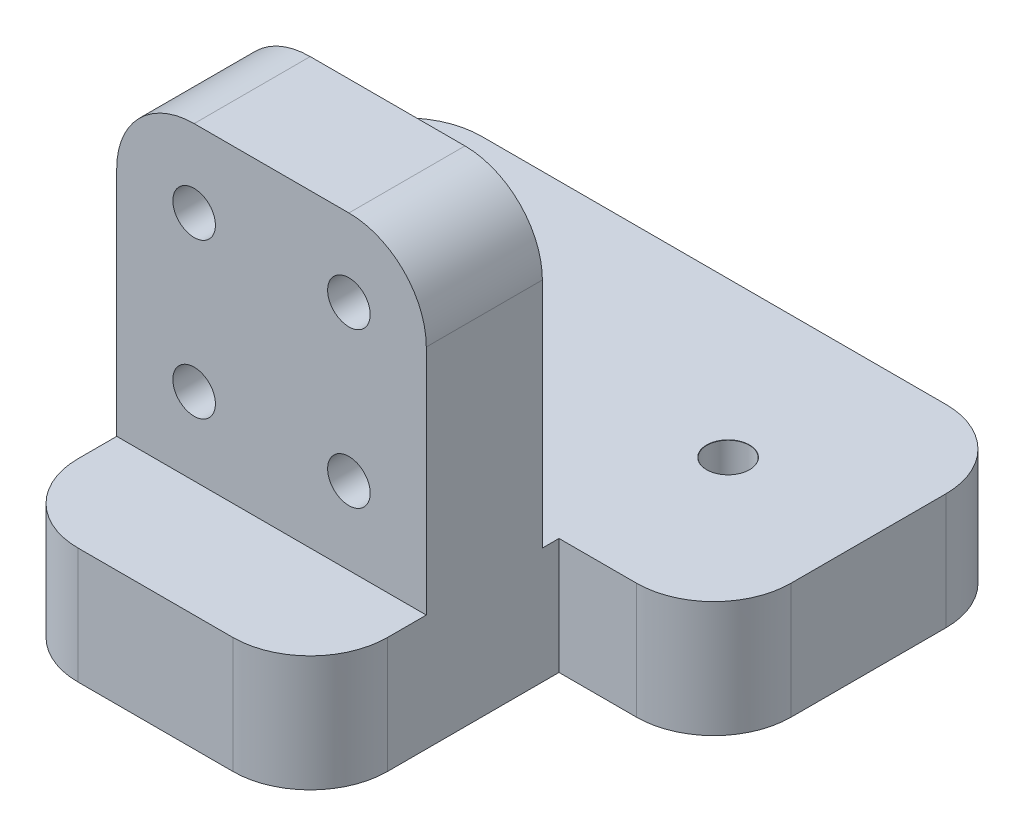
SolidWorks part; units mm, degrees
ref_plane "Front Plane" through (0, 0, 0) normal (0, 0, 1) x (1, 0, 0)
ref_plane "Top Plane" through (0, 0, 0) normal (0, 1, 0) x (1, 0, 0)
ref_plane "Right Plane" through (0, 0, 0) normal (1, 0, 0) x (0, 0, -1)
sketch "Sketch1" plane through (0, 0, 0) normal (0, 1, 0) x (1, 0, 0)
  line L1 (0, 0) -> (40, 0)
  line L7 (40, 0) -> (40, 32.15)
  line L8 (0, 0) -> (0, 32.15)
  line L13 (0, 32.15) -> (-20, 32.15)
  line L14 (-20, 32.15) -> (-20, 72.15)
  line L15 (-20, 72.15) -> (60, 72.15)
  line L16 (60, 72.15) -> (60, 32.15)
  line L17 (60, 32.15) -> (40, 32.15)
  line L18 (-1.85, 52.15) -> (41.85, 52.15) construction
  point P1 (41.85, 52.15)
  point P12 (-1.85, 52.15)
  point P13 (-20, 52.15)
  point P16 (20, 72.15)
  point P17 (20, 52.15)
  dimension "D1" = 40
  dimension "D2" = 52.15
  dimension "D3" = 40
  dimension "D4" = 43.7
  dimension "D5" = 20
extrude "Boss-Extrude1" add sketch "Sketch1" along normal blind 15 contours L1 region at (20, 0, -41.8084)
sketch "Sketch6" plane through (0, 15, 0) normal (0, 1, 0) x (1, 0, 0)
  point P0 (-1.85, 52.15)
  point P3 (41.85, 52.15)
hole_wizard "M5 Clearance Hole1" positions "Sketch6" profile "Sketch5" hole size "M5" standard "ANSI Metric" end condition through all
sketch "Sketch5" plane through (-1.85, 15, -52.15) normal (1, 0, 0) x (0, 0, 1)
  line L0 (0, 0) -> (0, 15)
  line L1 (0, 15) -> (2.75, 15)
  line L2 (2.75, 15) -> (2.75, 0.025)
  line L3 (2.75, 0.025) -> (2.775, 0)
  line L5 (2.775, 0) -> (0, 0)
  line L6 (-2.75, 0.025) -> (-2.775, 0) construction
  line L11 (0, -6.35) -> (0, 107.95) construction
  dimension "Thru Hole Dia." = 5.5
  dimension "Thru Hole Depth" = 15
  dimension "Near C'Sink Dia." = 5.55
  dimension "Near C'Sink Angle" = 90
sketch "Sketch8" plane through (0, 15, 0) normal (0, 1, 0) x (1, 0, 0)
  line L0 (0, 0) -> (0, 32.15) construction
  line L1 (0, 15) -> (40, 15)
  line L2 (0, 15) -> (0, 30)
  line L3 (0, 30) -> (40, 30)
  line L4 (40, 15) -> (40, 30)
  line L5 (40, 0) -> (40, 32.15) construction
  line L6 (0, 0) -> (40, 0) construction
  dimension "D1" = 15
  dimension "D2" = 15
extrude "Boss-Extrude2" add sketch "Sketch8" along normal blind 40
sketch "Sketch11" plane through (0, 0, -30) normal (0, 0, -1) x (-1, 0, 0)
  line L1 (-30, 45) -> (-10, 45) construction
  line L2 (-30, 45) -> (-30, 25) construction
  line L3 (-30, 25) -> (-10, 25) construction
  line L4 (-10, 45) -> (-10, 25) construction
  line L5 (-40, 55) -> (0, 55) construction
  line L6 (-40, 55) -> (-40, 15) construction
  point P1 (-30, 45)
  point P2 (-10, 25)
  point P85 (-30, 25)
  point P86 (-10, 45)
  point P93 (-30, 45)
  point P95 (-10, 45)
  point P103 (-30, 25)
  point P105 (-10, 25)
  point P110 (-20, 55)
  point P111 (-20, 45)
  point P114 (-40, 35)
  point P115 (-30, 35)
  dimension "D1" = 20
hole_wizard "M5 Clearance Hole2" positions "Sketch11" profile "Sketch10" hole size "M5" standard "ANSI Metric" end condition through all
sketch "Sketch10" plane through (10, 25, -30) normal (1, 0, 0) x (0, 1, 0)
  line L0 (0, 0) -> (0, 30)
  line L1 (0, 30) -> (2.75, 30)
  line L2 (2.75, 30) -> (2.75, 0.025)
  line L3 (2.75, 0.025) -> (2.775, 0)
  line L5 (2.775, 0) -> (0, 0)
  line L6 (-2.75, 0.025) -> (-2.775, 0) construction
  line L11 (0, -6.35) -> (0, 107.95) construction
  dimension "Thru Hole Dia." = 5.5
  dimension "Thru Hole Depth" = 30
  dimension "Near C'Sink Dia." = 5.55
  dimension "Near C'Sink Angle" = 90
fillet "Fillet2" radius 10 8 edges at (40, 55, -22.5) (0, 55, -22.5) (-20, 7.5, -32.15) (0, 7.5, 0) (40, 7.5, 0) (60, 7.5, -32.15) (60, 7.5, -72.15) (-20, 7.5, -72.15) first distance on face at (40, 21.25, -19.2875) first distance on face at (0, 21.25, -19.2875) first distance on face at (-10, 7.5, -32.15) first distance on face at (20, 7.5, 0) first distance on face at (50, 7.5, -32.15) first distance on face at (20, 7.5, -72.15)
